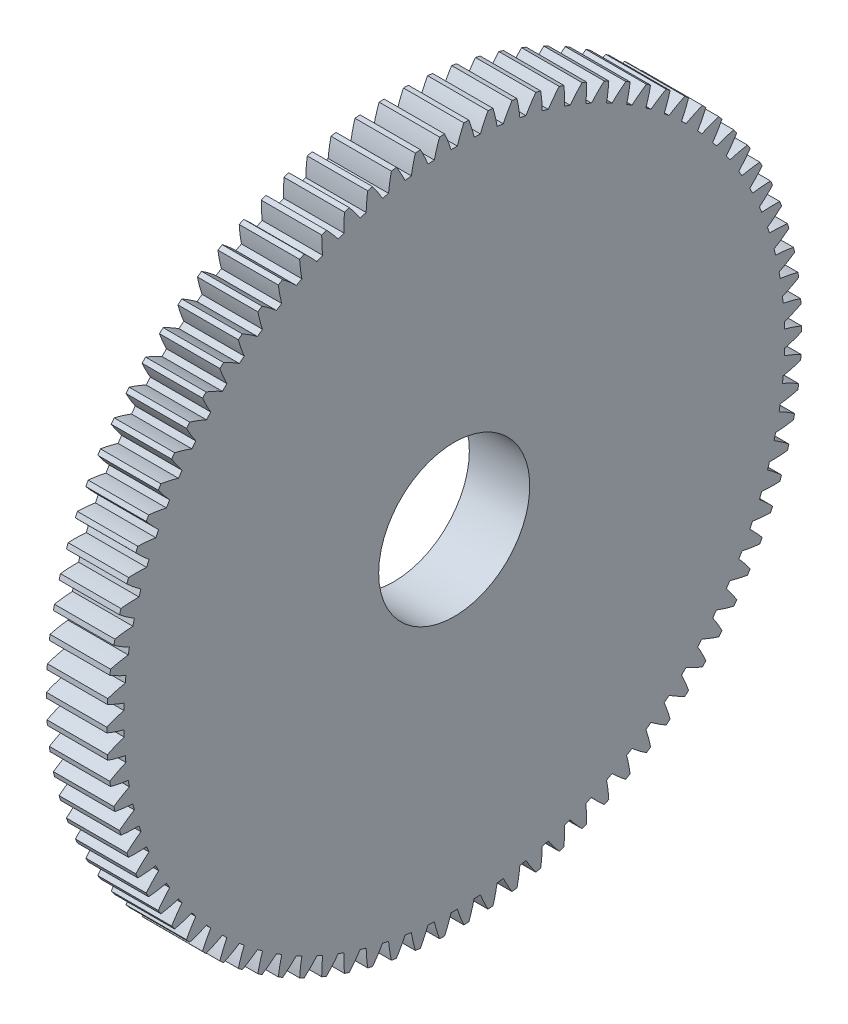
SolidWorks part; units mm, degrees
ref_plane "Plane1" through (0, 0, 0) normal (0, 0, 1) x (1, 0, 0)
ref_plane "Plane2" through (0, 0, 0) normal (0, 1, 0) x (1, 0, 0)
ref_plane "Plane3" through (0, 0, 0) normal (1, 0, 0) x (0, 0, -1)
sketch "HoldingSke" plane through (0, 0, 0) normal (0, 1, 0) x (1, 0, 0)
  line L0 (0, 0) -> (0, -2)
  line L1 (-15, 0) -> (100, 0) construction
  line L2 (0, 0) -> (-2.1039, 2.3779)
  line L3 (0, 0) -> (-11.863, 4.5341)
  line L4 (0, 0) -> (0, 8.636)
  line L5 (0, 0) -> (-46.8476, -17.4728)
  line L6 (0, 0) -> (-3.3159, -2.2372)
  line L7 (-2.1039, 2.3779) -> (8.6586, 51.2059)
  line L8 (-76.2, 54.61) -> (-74.4, 54.61)
  line L9 (-71.009, 38.7566) -> (-53.1078, 45.2721)
  line L10 (-76.2, 71.12) -> (104.1128, 71.12)
  line L11 (0, 0) -> (-4, 0)
  line L12 (-76.2, 101.6) -> (-76.181, 101.6)
  line L13 (24.9733, 27.94) -> (52.9518, 28.4284)
  line L14 (24.9733, 27.94) -> (24.9743, 27.94)
  line L15 (24.9733, 27.94) -> (100.4006, 29.5858)
  line L16 (-63.627, -0.5) -> (-12.827, -0.5)
  circle A0 centre (0, 0) radius 5
  circle A1 centre (0, 0) radius 21.874
  circle A2 centre (0, 0) radius 37.5
  circle A3 centre (0, 0) radius 5
  dimension "Num_teeth" = 90
  dimension "Pitch_radius" = 180.3128
  dimension "Width" = 4
  dimension "Thickness" = 4
sketch "BasProSke" plane through (0, 0, 0) normal (0, 1, 0) x (1, 0, 0)
  line L0 (-10, 0) -> (60, 0) construction
  line L1 (0, 0) -> (0, 23)
  line L2 (0, 0) -> (4, 0)
  line L3 (4, 0) -> (4, 23)
  line L4 (4, 23) -> (0, 23)
  dimension "Thickness" = 4
  dimension "Diameter" = 46
revolve "Base-Revolve" add sketch "BasProSke" angle 360 about L0
sketch "TooCutSke" plane through (0, 0, 0) normal (1, 0, 0) x (0, 0, -1)
  line L1 (0, 0) -> (0, 107) construction
  line L2 (0, 0) -> (-0.4259, 22.496) construction
  line L3 (0, 0) -> (-1.5703, 44.9668) construction
  line L4 (-0.4259, 22.496) -> (-0.7851, 22.4834) construction
  arc A0 (0.2085, 21.873) -> (-0.2085, 21.873) centre (0, 0) ccw
  arc A1 (0.6483, 23.0163) -> (-0.6483, 23.0163) centre (0, 0) ccw
  circle A2 centre (0, 0) radius 22.5 construction
  circle A3 centre (0, 0) radius 21.1431 construction
  arc A4 (-0.2085, 21.873) -> (-0.6483, 23.0163) centre (-8.8088, 19.2207) ccw
  arc A5 (0.6483, 23.0163) -> (0.2085, 21.873) centre (8.8088, 19.2207) ccw
extrude "ToothCut" cut sketch "TooCutSke" along normal through all
fillet "Breaks" [suppressed] radius 0.01 tangent propagation no
fillet "RootFillets" [suppressed] radius 0.126
pattern_circular "TeethCuts" count 90 every 4 about axis through (-10, 0, 0) along (1, 0, 0) of "ToothCut", "RootFillets", "Breaks"
sketch "HubNeaOneSke" plane through (0, 0, 0) normal (-1, 0, 0) x (0, 0, 1)
  circle A0 centre (0, 0) radius 21.874
  dimension "Diameter" = 43.748
extrude "HubNearOne" [suppressed] add sketch "HubNeaOneSke" along normal blind 46.0001
sketch "HubNeaBotSke" plane through (0, 0, 0) normal (-1, 0, 0) x (0, 0, 1)
  circle A0 centre (0, 0) radius 21.874
  dimension "Diameter" = 43.748
extrude "HubNearBoth" [suppressed] add sketch "HubNeaBotSke" along normal blind 23
ref_plane "FarPln" through (4, 0, 0) normal (1, 0, 0) x (0, 0, -1)
sketch "HubFarSke" plane through (4, 0, 0) normal (1, 0, 0) x (0, 0, -1)
  circle A0 centre (0, 0) radius 21.874
  dimension "Diameter" = 43.748
extrude "HubFar" [suppressed] add sketch "HubFarSke" along normal blind 23
sketch "BorSke" plane through (0, 0, 0) normal (1, 0, 0) x (0, 0, -1)
  circle A0 centre (0, 0) radius 5
  dimension "Diameter" = 10
extrude "Bore" cut sketch "BorSke" along normal mid plane 100.0001
sketch "KeySke" plane through (0, 0, 0) normal (1, 0, 0) x (0, 0, -1)
  line L0 (-2, 0) -> (-2, 6.8)
  line L1 (-2, 6.8) -> (2, 6.8)
  line L2 (2, 6.8) -> (2, 0)
  line L3 (0, 0) -> (0, 34) construction
  line L4 (-2, 0) -> (2, 0)
  dimension "Width" = 4
extrude "Keyway" [suppressed] cut sketch "KeySke" along normal mid plane 100.0001
pattern_circular "Keyway2" [suppressed] count 2 every 90 about axis through (-10, 0, 0) along (1, 0, 0) reverse direction yes
equation "' \"Module@HoldingSke\" = 6.35"
equation "' \"Num_teeth@HoldingSke\" = 12"
equation "' \"Ap@HoldingSke\" =  20"
equation "' \"Ap@HoldingSke\" = 20"
equation "' \"Width@HoldingSke\" = 0.5 * 25.4"
equation "' \"Hub_dia@HoldingSke\"= 1 * 25.4"
equation "' \"Hub_dia@HoldingSke\" = 1 * 25.4"
equation "' \"Overall_len@HoldingSke\" = 1.0 * 25.4"
equation "' \"Bore@HoldingSke\" = 0.75 * 25.4"
equation "' \"T_dim@HoldingSke\" = 0.1 * 25.4"
equation "' \"Width@KeySke\" = 0.25 * 25.4"
equation "' \"Show_teeth@HoldingSke\" = 13"
equation "' \"Backlash@HoldingSke\" = 0.009 * 25.4"
equation "' \"Addendum_fac@HoldingSke\" = 1.0"
equation "' \"Dedendum_fac@HoldingSke\" = 1.25"
equation "' \"Dedendum_add@HoldingSke\" = 0.00005 * 25.4"
equation "' \"Clearance_fac@HoldingSke\" = 0.25"
equation "\"Pitch@HoldingSke\" = 1 / \"Module@HoldingSke\""
equation "\"Overcut_dia@TooCutSke\" = (\"Num_teeth@HoldingSke\" + 2 * \"Addendum_fac@HoldingSke\") / \"Pitch@HoldingSke\" + 0.002 * 25.4"
equation "\"Pitch_dia@TooCutSke\" = \"Num_teeth@HoldingSke\" / \"Pitch@HoldingSke\""
equation "\"Base_dia@TooCutSke\" = \"Num_teeth@HoldingSke\" / \"Pitch@HoldingSke\" * cos((\"Ap@HoldingSke\"  * 3.14159265 / 180))"
equation "\"Root_dia@TooCutSke\" = (\"Num_teeth@HoldingSke\" + 2) / \"Pitch@HoldingSke\" - 2 * (\"Addendum_fac@HoldingSke\" + \"Dedendum_fac@HoldingSke\") / \"Pitch@HoldingSke\" - \"Dedendum_add@HoldingSke\" * 2"
equation "\"Half_ang@TooCutSke\" = 180 / \"Num_teeth@HoldingSke\""
equation "\"Half_CT@TooCutSke\" = \"Num_teeth@HoldingSke\" / \"Pitch@HoldingSke\" * sin((3.14159265 / 2 / \"Num_teeth@HoldingSke\")) / 2 - 7 * \"Backlash@HoldingSke\" / 4"
equation "\"Flank_rad@TooCutSke\" = \"Num_teeth@HoldingSke\" / \"Pitch@HoldingSke\" / 5"
equation "\"Radius@RootFillets\" = \"Clearance_fac@HoldingSke\" / \"Pitch@HoldingSke\" + \"Dedendum_add@HoldingSke\""
equation "\"Break_rad@Breaks\" = 0.02 / \"Pitch@HoldingSke\""
equation "\"Thickness@HoldingSke\" = \"Width@HoldingSke\""
equation "\"OAL@HoldingSke\" = \"Thickness@HoldingSke\""
equation "\"MHD@HoldingSke\" = (\"Num_teeth@HoldingSke\" + 2) / \"Pitch@HoldingSke\" - 2 * (\"Addendum_fac@HoldingSke\" + \"Dedendum_fac@HoldingSke\")  / \"Pitch@HoldingSke\" - \"Dedendum_add@HoldingSke\" * 2"
equation "\"MBD@HoldingSke\" = (\"Num_teeth@HoldingSke\" + 2) / \"Pitch@HoldingSke\" - 2 * (\"Addendum_fac@HoldingSke\" + \"Dedendum_fac@HoldingSke\")  / \"Pitch@HoldingSke\" - \"Dedendum_add@HoldingSke\" * 2 - 0.002 * 25.4"
equation "\"MHD@HoldingSke\" = ((sgn( \"MHD@HoldingSke\" - \"Hub_dia@HoldingSke\" )-1)*( \"MHD@HoldingSke\" - \"Hub_dia@HoldingSke\" ))/-2+ \"Hub_dia@HoldingSke\""
equation "\"MBD@HoldingSke\" = ((sgn( \"MBD@HoldingSke\" - \"Bore@HoldingSke\" )-1)*( \"MBD@HoldingSke\" - \"Bore@HoldingSke\" ))/-2+ \"Bore@HoldingSke\""
equation "\"OAL@HoldingSke\" = ((sgn( \"OAL@HoldingSke\" - \"Overall_len@HoldingSke\" )+1)*( \"OAL@HoldingSke\" - \"Overall_len@HoldingSke\" ))/2 + \"Overall_len@HoldingSke\" + 0.000002 * 25.4"
equation "\"Num_teeth@TeethCuts\" = int( \"Show_teeth@HoldingSke\" ) + 1"
equation "\"Num_teeth@TeethCuts\" = ((sgn( \"Num_teeth@TeethCuts\" - \"Num_teeth@HoldingSke\" )-1)*( \"Num_teeth@TeethCuts\" - \"Num_teeth@HoldingSke\" ))/-2+ \"Num_teeth@HoldingSke\""
equation "\"Num_teeth@TeethCuts\" = ((sgn( \"Num_teeth@TeethCuts\" - 2.0)+1)*( \"Num_teeth@TeethCuts\" - 2.0))/2 +2.0"
equation "\"Angle@TeethCuts\" = 360.0 / \"Num_teeth@HoldingSke\""
equation "\"Diameter@BasProSke\" = (\"Num_teeth@HoldingSke\" + 2 * \"Addendum_fac@HoldingSke\") / \"Pitch@HoldingSke\""
equation "\"Thickness@BasProSke\"  = \"Thickness@HoldingSke\""
equation "' \"Fillet_rad@BasProSke\" =  \"Thickness@HoldingSke\" * 0.05"
equation "' \"Fillet_rad@BasProSke\" = \"Thickness@HoldingSke\" * 0.05"
equation "\"MHD@HoldingSke\" = ((sgn( \"MHD@HoldingSke\" - \"Root_dia@TooCutSke\" )-1)*( \"MHD@HoldingSke\" - \"Root_dia@TooCutSke\" ))/-2+ \"Root_dia@TooCutSke\""
equation "\"Diameter@HubNeaOneSke\" = \"MHD@HoldingSke\""
equation "\"Length@HubNearOne\" = \"OAL@HoldingSke\" - \"Thickness@BasProSke\""
equation "\"Diameter@HubNeaBotSke\" = \"MHD@HoldingSke\""
equation "\"Length@HubNearBoth\" = ( \"OAL@HoldingSke\" - \"Thickness@BasProSke\" ) / 2.0"
equation "\"Thickness@FarPln\" = \"Thickness@BasProSke\""
equation "\"Diameter@HubFarSke\" = \"MHD@HoldingSke\""
equation "\"Length@HubFar\" = ( \"OAL@HoldingSke\" - \"Thickness@BasProSke\" ) / 2.0"
equation "\"Diameter@BorSke\" = \"MBD@HoldingSke\""
equation "\"D1@Bore\" = \"OAL@HoldingSke\" * 2.0"
equation "\"D1@Keyway\" = \"OAL@HoldingSke\" * 2.0"
equation "\"Offset@KeySke\" = \"T_dim@HoldingSke\" + \"MBD@HoldingSke\" / 2.0"
